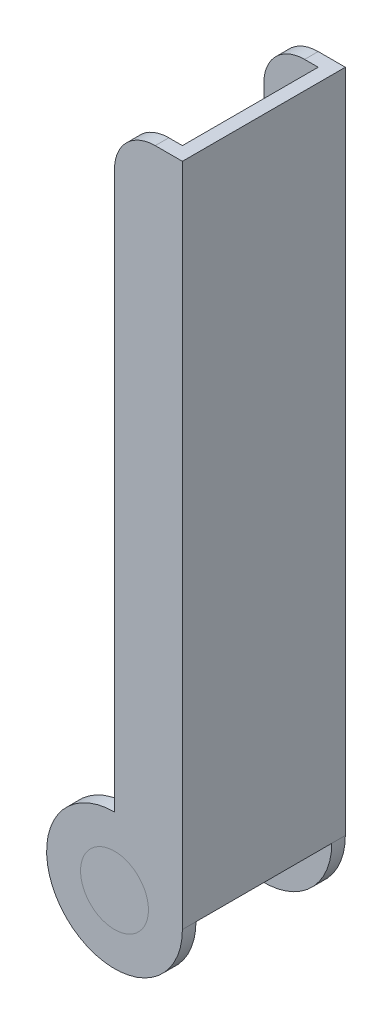
SolidWorks part; units mm, degrees
ref_plane "Front Plane" through (0, 0, 0) normal (0, 0, 1) x (1, 0, 0)
ref_plane "Top Plane" through (0, 0, 0) normal (0, 1, 0) x (1, 0, 0)
ref_plane "Right Plane" through (0, 0, 0) normal (1, 0, 0) x (0, 0, -1)
sketch "Sketch1" plane through (0, 0, 0) normal (0, 0, 1) x (1, 0, 0)
  line L0 (5, 0) -> (5, 49)
  line L1 (0, 2.5) -> (0, 49)
  line L2 (0, 49) -> (5, 49)
  line L3 (4, 49) -> (4, -3)
  circle A0 centre (0, 0) radius 2.5
  circle A1 centre (0, 0) radius 5
  dimension "D1" = 5
  dimension "D2" = 10
  dimension "D3" = 49
  dimension "D4" = 1
extrude "Boss-Extrude1" add sketch "Sketch1" along normal blind 12 contours A1 L0 L2 L3 | A0 region at (4.5042, 25.5167, 0) region at (0, 0, 0)
extrude "Boss-Extrude2" add sketch "Sketch1<4>" along normal blind 1 contours L3 A1 A0 | A1 L3 | A1 L3 L2 L1 region at (4.4036, 0, 0) region at (-4.3518, -2.1759, 0) region at (2.0141, 26.6952, 0)
sketch "Sketch1<4>" plane through (0, 0, 0) normal (0, 0, 1) x (1, 0, 0) same geometry as "Sketch1"
extrude "Boss-Extrude3" add sketch "Sketch1<5>" along normal blind 1 from offset 11 contours L3 A1 A0 | A1 L3 L2 L1 | A1 L3 region at (4.4036, 0, 0) region at (-4.3518, -2.1759, 0) region at (2.0141, 26.6952, 0)
sketch "Sketch1<5>" plane through (0, 0, 0) normal (0, 0, 1) x (1, 0, 0) same geometry as "Sketch1"
fillet "Fillet1" radius 3 2 edges at (0, 49, 11.5) (0, 49, 0.5) tangent propagation no
